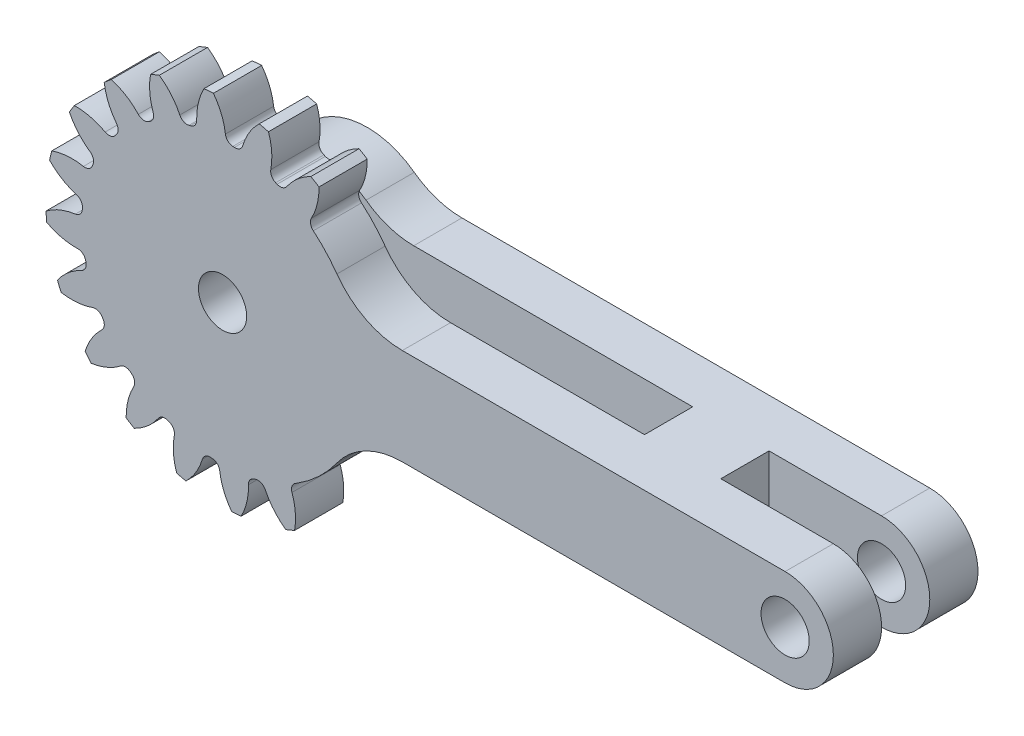
SolidWorks part; units mm, degrees
material "3.0205 (EN-AW 1200)"
ref_plane "Piano frontale" through (0, 0, 0) normal (0, 0, 1) x (1, 0, 0)
ref_plane "Piano superiore" through (0, 0, 0) normal (0, 1, 0) x (1, 0, 0)
ref_plane "Piano destro" through (0, 0, 0) normal (1, 0, 0) x (0, 0, -1)
sketch "Schizzo1" plane through (0, 0, 0) normal (0, 0, 1) x (1, 0, 0)
  line L0 (-10, 0) -> (-10, 34.7639) construction
  line L1 (-10, 0) -> (2.256, 33.6731) construction
  line L2 (-11, 0) -> (-9.3969, 0) construction
  line L3 (-9.3969, 0) -> (-10.1985, 0)
  line L4 (-10.1985, 0) -> (-11, 0)
  line L5 (-10.1985, 0) -> (-8.6584, -3.6517) construction
  line L6 (-10.1985, 0) -> (-9.6851, -1.2172)
  line L7 (-9.6851, -1.2172) -> (-9.1717, -2.4344)
  line L8 (-9.1717, -2.4344) -> (-8.6584, -3.6517)
  line L9 (-8.6584, -3.6517) -> (-8.145, -4.8689)
  line L10 (0, 0) -> (-10.9661, -0.8631) construction
  line L11 (0, 0) -> (-10.1985, 0) construction
  line L12 (0, 0) -> (35, 0) construction
  line L14 (0, 3) -> (35, 3)
  line L15 (0, -3) -> (35, -3)
  circle A0 centre (0, 0) radius 10
  circle A1 centre (0, 0) radius 9.3969
  circle A2 centre (0, 0) radius 11
  circle A3 centre (0, 0) radius 8.75
  arc A4 (-10.9909, -0.4476) -> (-8.7445, 0.3105) centre (-8.6584, -3.6517) cw
  arc A5 (-10.9256, -1.2772) -> (-8.5882, -1.6747) centre (-9.123, 2.2522) ccw
  circle A6 centre (0, 0) radius 9.4893 construction
  circle A7 centre (-9.1676, -2.45) radius 0.7393 construction
  arc A8 (0, 3) -> (0, -3) centre (0, 0) ccw
  arc A9 (35, -3) -> (35, 3) centre (35, 0) ccw
  circle A10 centre (0, 0) radius 1.5
  circle A11 centre (35, 0) radius 1.5
  point P28 (17.5, 0)
  dimension "D1" = 20
  dimension "D3" = 18.7939
  dimension "D4" = 22
  dimension "D5" = 17.5
  dimension "D7" = 1.4787
  dimension "D8" = 3
  dimension "D9" = 3
  dimension "D2" = 20
  dimension "D6" = 4.5
  dimension "D10" = 6
  dimension "D11" = 35
sketch "Schizzo2" plane through (0, 0, 0) normal (0, 0, 1) x (1, 0, 0)
  circle A0 centre (0, 0) radius 8.75 construction
  circle A1 centre (0, 0) radius 8.75
  circle A2 centre (0, 0) radius 1.5
  dimension "D1" = 3
extrude "Estrusione-Estrusione1" add sketch "Schizzo2" along normal blind 4.5 and the other way blind 4.5
sketch "Schizzo3" plane through (0, 0, 0) normal (0, 0, 1) x (1, 0, 0)
  arc A0 (-10.9256, -1.2772) -> (-8.5882, -1.6747) centre (-9.123, 2.2522) ccw construction
  arc A1 (-8.7445, 0.3105) -> (-10.9909, -0.4476) centre (-8.6584, -3.6517) ccw construction
  arc A2 (-10.9256, -1.2772) -> (-8.5882, -1.6747) centre (-9.123, 2.2522) ccw construction
  arc A3 (-8.7445, 0.3105) -> (-10.9909, -0.4476) centre (-8.6584, -3.6517) ccw construction
  circle A4 centre (0, 0) radius 8.75 construction
  circle A5 centre (0, 0) radius 11 construction
  arc A6 (-8.7475, 0.2105) -> (-8.6069, -1.5763) centre (0, 0) ccw
  arc A7 (-10.9853, -0.568) -> (-10.9389, -1.1575) centre (0, 0) ccw
  arc A8 (-8.7475, 0.2105) -> (-10.9853, -0.568) centre (-8.6584, -3.6517) ccw
  arc A9 (-10.9389, -1.1575) -> (-8.6069, -1.5763) centre (-9.123, 2.2522) ccw
  arc A10 (-10.8801, -1.1882) -> (-8.6017, -1.5756) centre (-9.123, 2.2522) ccw construction
  arc A11 (-8.7423, 0.2106) -> (-10.932, -0.5285) centre (-8.6584, -3.6517) ccw construction
  dimension "D1" = 0.1
  dimension "D2" = 0.1
extrude "Estrusione-Estrusione2" add sketch "Schizzo3" along normal blind 4.5
fillet "Raccordo1" radius 0.5 1 edges at (-8.7475, 0.2105, 2.25)
fillet "Raccordo2" radius 0.5 1 edges at (-8.6069, -1.5763, 2.25)
pattern_circular "RipetizioneCircolare1" count 20 over 360 about axis through (0, 0, -4.5) along (0, 0, 1) of "Estrusione-Estrusione2", "Raccordo1", "Raccordo2"
extrude "Estrusione-Estrusione4" add sketch "Schizzo1" along normal blind 4.5 and the other way blind 4.5 contours L14 A8 L15 A3 A10 | A3 L15 A1 L14 | A1 L15 A0 L14 | L15 A2 L14 A0 | L15 A9 L14 A2 A11 region at (8.9025, 0, 0) region at (9.5392, 0, 0) region at (10.3533, 0, 0) region at (3.4635, 0, 0) region at (23.6109, 0, 0)
ref_plane "Piano1" through (10.073, -3, 4.5) normal (1, 0, 0) x (0, 0, -1)
ref_plane "Piano2" through (35, 3, 4.5) normal (1, 0, 0) x (0, 0, -1)
sketch "Schizzo8" plane through (0, 3, 0) normal (0, 1, 0) x (1, 0, 0)
  line L0 (38, -1.5) -> (-11.75, -1.5) construction
  line L1 (38, -4.5) -> (38, 4.5) construction
  line L2 (9.3446, -4.5) -> (35, -4.5) construction
  line L3 (38, 1.5) -> (-8.75, 1.5) construction
  line L4 (-8.75, 4.5) -> (-8.75, 0) construction
  line L5 (8.2196, 4.5) -> (35, 4.5) construction
  line L6 (38, -1.5) -> (28, -1.5)
  line L7 (28, -1.5) -> (28, 1.5)
  line L8 (28, 1.5) -> (38, 1.5)
  line L9 (38, 1.5) -> (38, -1.5)
  line L10 (-11.75, -1.5) -> (23.25, -1.5)
  line L11 (23.25, -1.5) -> (23.25, 1.5)
  line L14 (23.25, 1.5) -> (-11.75, 1.5)
  line L15 (-11.75, 1.5) -> (-11.75, -1.5)
  dimension "D1" = 3
  dimension "D2" = 3
  dimension "D3" = 10
  dimension "D4" = 35
extrude "Taglio-Estrusione2" cut sketch "Schizzo8" against normal blind 15 and the other way blind 15
sketch "Schizzo9" plane through (0, 0, -4.5) normal (0, 0, -1) x (-1, 0, 0)
  line L0 (-8.2196, 3) -> (-3.9196, 3)
  line L1 (-8.2196, -3) -> (-3.9196, -3)
  arc A0 (-8.2196, 3) -> (-8.2196, -3) centre (0, 0) cw
  arc A1 (-8.2196, -3) -> (-8.2196, 3) centre (0, 0) ccw construction
  arc A2 (-3.9196, 3) -> (-3.9196, -3) centre (0, 0) cw
  dimension "D1" = 4.3
  dimension "D2" = 4.3
extrude "Taglio-Estrusione3" cut sketch "Schizzo9" against normal blind 3.3 contours L1 A2 L0 A0
sketch "Schizzo10" plane through (0, 0, 4.5) normal (0, 0, 1) x (1, 0, 0)
  line L0 (9.3446, 3) -> (8.2196, 3)
  line L1 (4.6249, -7.4278) -> (6.1628, -9.8977)
  line L3 (10.073, -3) -> (8.2196, -3)
  line L4 (6.1628, -9.8977) -> (11.505, -6.5714)
  line L5 (11.505, -6.5714) -> (10.073, -3)
  line L6 (5.7196, 6.6219) -> (8.6341, 8.4809)
  line L7 (8.6341, 8.4809) -> (11.505, 3.9802)
  line L8 (11.505, 3.9802) -> (9.3446, 3)
  arc A0 (5.7196, 6.6219) -> (8.2196, 3) centre (0, 0) cw
  arc A2 (8.2196, -3) -> (4.6249, -7.4278) centre (0, 0) cw
  dimension "D1" = 2.9146
  dimension "D6" = 8.75
  dimension "D2" = 5.3384
  dimension "D3" = 2.1603
  dimension "D4" = 3.8478
  dimension "D5" = 6.2932
  dimension "D7" = 2.9095
extrude "Taglio-Estrusione4" cut sketch "Schizzo10" against normal blind 3.3
fillet "Raccordo3" radius 5 1 edges at (8.2196, 3, 3)
fillet "Raccordo4" radius 5 1 edges at (8.2196, -3, 3)
fillet "Raccordo5" radius 5 1 edges at (3.9196, -3, -3)
fillet "Raccordo6" radius 5 1 edges at (3.9196, 3, -3)
equation "\"z\"= 20'Numero denti"
equation "\"m\"= 1'Modulo"
equation "\"p\"= \"m\" * pi'Passo"
equation "\"dp\"= \"z\" * \"m\"'Diametro primitiva"
equation "\"a\"= \"m\"'Addendum"
equation "\"de\"= \"dp\" + 2 * \"m\"'Diametro esterno"
equation "\"d\"= 1.25 * \"m\"'Dedendum"
equation "\"di\"= \"dp\" - 2.5 * \"m\"'Diametro interno"
equation "\"alpha\"= 20'Angolo di pressione"
equation "\"D1@Schizzo1\"=\"dp\""
equation "\"D2@Schizzo1\"=\"alpha\""
equation "\"D4@Schizzo1\"=\"de\""
equation "\"D5@Schizzo1\"=\"di\""
equation "\"beta\"= ( \"p\" * 360 ) / ( 4 * pi * \"dp\" )"
equation "\"D6@Schizzo1\"=\"beta\""
equation "\"D1@RipetizioneCircolare1\"= \"z\""
